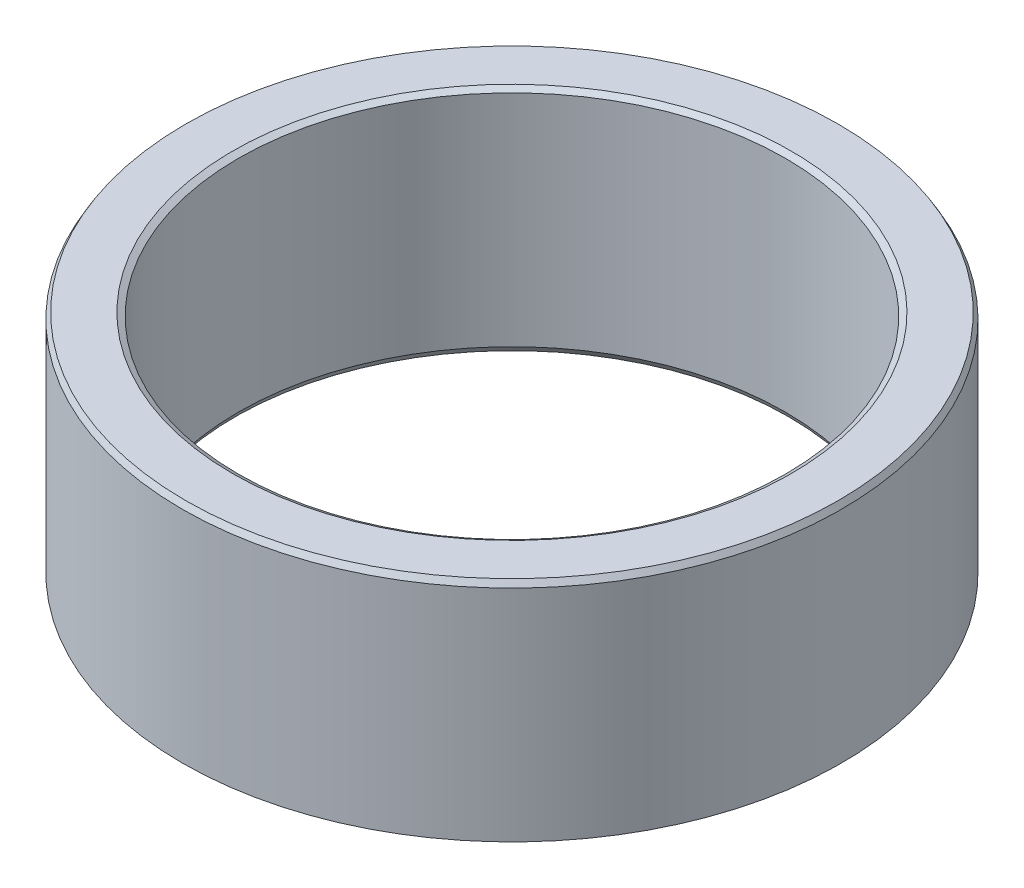
SolidWorks part; units mm, degrees
ref_plane "Front Plane" through (0, 0, 0) normal (0, 0, 1) x (1, 0, 0)
ref_plane "Top Plane" through (0, 0, 0) normal (0, 1, 0) x (1, 0, 0)
ref_plane "Right Plane" through (0, 0, 0) normal (1, 0, 0) x (0, 0, -1)
sketch "Sketch1" plane through (0, 0, 0) normal (0, 1, 0) x (1, 0, 0)
  circle A0 centre (0, 0) radius 52.5
  dimension "SLEEVE_OD" = 105
extrude "Boss-Extrude1" add sketch "Sketch1" along normal blind 36.4789
sketch "Sketch2" plane through (0, 0, 0) normal (0, 1, 0) x (1, 0, 0)
  circle A0 centre (0, 0) radius 43.5735
  dimension "BORE_D" = 87.1471
extrude "Cut-Extrude1" cut sketch "Sketch2" along normal through all
chamfer "Chamfer1" distance 0.9266 angle 30 4 edges at (0, 36.4789, 43.5735) (0, 0, 43.5735) (0, 0, 52.5) (0, 36.4789, 52.5) first distance on face at (0, 36.4789, 43.5735) first distance on face at (0, 0, 43.5735) first distance on face at (0, 36.4789, 52.5)
